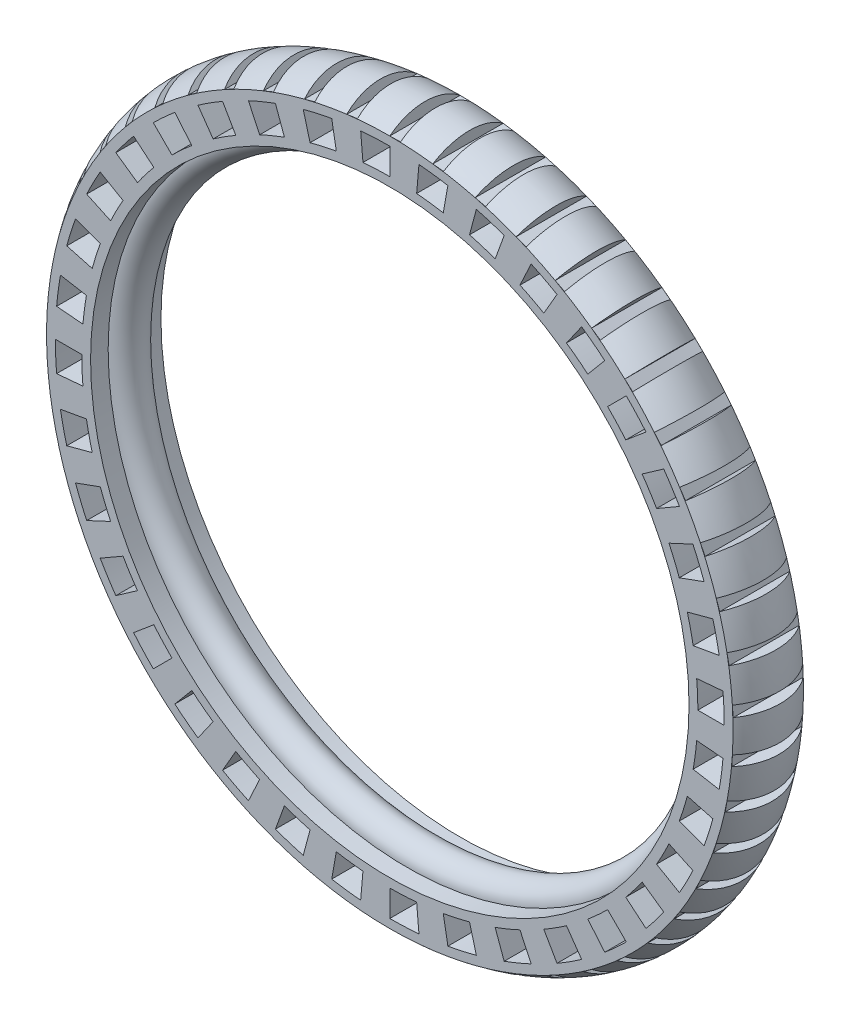
SolidWorks part; units mm, degrees
material "硅橡胶"
ref_plane "前视基准面" through (0, 0, 0) normal (0, 0, 1) x (1, 0, 0)
ref_plane "上视基准面" through (0, 0, 0) normal (0, 1, 0) x (1, 0, 0)
ref_plane "右视基准面" through (0, 0, 0) normal (1, 0, 0) x (0, 0, -1)
sketch "草图1" plane through (0, 0, 0) normal (0, 1, 0) x (1, 0, 0)
  line L0 (0, 0) -> (-43.398, 0) construction
  line L1 (0, 0) -> (0, 10.7341) construction
  line L2 (-34, 2) -> (-34, 4)
  line L3 (-34, 4) -> (-39, 4)
  line L4 (-34, -2) -> (-34, -4)
  line L5 (-34, -4) -> (-39, -4)
  arc A0 (-34, -2) -> (-34, 2) centre (-34, 0) ccw
  arc A1 (-39, 4) -> (-39, -4) centre (-34, 0) ccw
  dimension "D1" = 4
  dimension "D4" = 5
  dimension "D2" = 34
  dimension "D3" = 2
revolve "旋转1" add sketch "草图1" angle 360 about L1
sketch "草图2" plane through (0, 0, -4) normal (0, 0, -1) x (-1, 0, 0)
  line L0 (0, 0) -> (0, 48.0881) construction
  line L1 (0, 35) -> (0, 38)
  line L2 (3.0505, 34.8668) -> (3.3119, 37.8554)
  line L3 (6.0777, 34.4683) -> (6.5986, 37.4227)
  line L4 (9.0587, 33.8074) -> (9.8351, 36.7052)
  line L5 (11.9707, 32.8892) -> (12.9968, 35.7083)
  line L6 (14.7916, 31.7208) -> (16.0595, 34.4397)
  line L7 (17.5, 30.3109) -> (19, 32.909)
  line L8 (20.0752, 28.6703) -> (21.7959, 31.1278)
  line L9 (22.4976, 26.8116) -> (24.4259, 29.1097)
  line L10 (24.7487, 24.7487) -> (26.8701, 26.8701)
  line L11 (26.8116, 22.4976) -> (29.1097, 24.4259)
  line L12 (28.6703, 20.0752) -> (31.1278, 21.7959)
  line L13 (30.3109, 17.5) -> (32.909, 19)
  line L14 (31.7208, 14.7916) -> (34.4397, 16.0595)
  line L15 (32.8892, 11.9707) -> (35.7083, 12.9968)
  line L16 (33.8074, 9.0587) -> (36.7052, 9.8351)
  line L17 (34.4683, 6.0777) -> (37.4227, 6.5986)
  line L18 (34.8668, 3.0505) -> (37.8554, 3.3119)
  line L19 (35, 0) -> (38, 0)
  line L20 (34.8668, -3.0505) -> (37.8554, -3.3119)
  line L21 (34.4683, -6.0777) -> (37.4227, -6.5986)
  line L22 (33.8074, -9.0587) -> (36.7052, -9.8351)
  line L23 (32.8892, -11.9707) -> (35.7083, -12.9968)
  line L24 (31.7208, -14.7916) -> (34.4397, -16.0595)
  line L25 (30.3109, -17.5) -> (32.909, -19)
  line L26 (28.6703, -20.0752) -> (31.1278, -21.7959)
  line L27 (26.8116, -22.4976) -> (29.1097, -24.4259)
  line L28 (24.7487, -24.7487) -> (26.8701, -26.8701)
  line L29 (22.4976, -26.8116) -> (24.4259, -29.1097)
  line L30 (20.0752, -28.6703) -> (21.7959, -31.1278)
  line L31 (17.5, -30.3109) -> (19, -32.909)
  line L32 (14.7916, -31.7208) -> (16.0595, -34.4397)
  line L33 (11.9707, -32.8892) -> (12.9968, -35.7083)
  line L34 (9.0587, -33.8074) -> (9.8351, -36.7052)
  line L35 (6.0777, -34.4683) -> (6.5986, -37.4227)
  line L36 (3.0505, -34.8668) -> (3.3119, -37.8554)
  line L37 (0, -35) -> (0, -38)
  line L38 (-3.0505, -34.8668) -> (-3.3119, -37.8554)
  line L39 (-6.0777, -34.4683) -> (-6.5986, -37.4227)
  line L40 (-9.0587, -33.8074) -> (-9.8351, -36.7052)
  line L41 (-11.9707, -32.8892) -> (-12.9968, -35.7083)
  line L42 (-14.7916, -31.7208) -> (-16.0595, -34.4397)
  line L43 (-17.5, -30.3109) -> (-19, -32.909)
  line L44 (-20.0752, -28.6703) -> (-21.7959, -31.1278)
  line L45 (-22.4976, -26.8116) -> (-24.4259, -29.1097)
  line L46 (-24.7487, -24.7487) -> (-26.8701, -26.8701)
  line L47 (-26.8116, -22.4976) -> (-29.1097, -24.4259)
  line L48 (-28.6703, -20.0752) -> (-31.1278, -21.7959)
  line L49 (-30.3109, -17.5) -> (-32.909, -19)
  line L50 (-31.7208, -14.7916) -> (-34.4397, -16.0595)
  line L51 (-32.8892, -11.9707) -> (-35.7083, -12.9968)
  line L52 (-33.8074, -9.0587) -> (-36.7052, -9.8351)
  line L53 (-34.4683, -6.0777) -> (-37.4227, -6.5986)
  line L54 (-34.8668, -3.0505) -> (-37.8554, -3.3119)
  line L55 (-35, 0) -> (-38, 0)
  line L56 (-34.8668, 3.0505) -> (-37.8554, 3.3119)
  line L57 (-34.4683, 6.0777) -> (-37.4227, 6.5986)
  line L58 (-33.8074, 9.0587) -> (-36.7052, 9.8351)
  line L59 (-32.8892, 11.9707) -> (-35.7083, 12.9968)
  line L60 (-31.7208, 14.7916) -> (-34.4397, 16.0595)
  line L61 (-30.3109, 17.5) -> (-32.909, 19)
  line L62 (-28.6703, 20.0752) -> (-31.1278, 21.7959)
  line L63 (-26.8116, 22.4976) -> (-29.1097, 24.4259)
  line L64 (-24.7487, 24.7487) -> (-26.8701, 26.8701)
  line L65 (-22.4976, 26.8116) -> (-24.4259, 29.1097)
  line L66 (-20.0752, 28.6703) -> (-21.7959, 31.1278)
  line L67 (-17.5, 30.3109) -> (-19, 32.909)
  line L68 (-14.7916, 31.7208) -> (-16.0595, 34.4397)
  line L69 (-11.9707, 32.8892) -> (-12.9968, 35.7083)
  line L70 (-9.0587, 33.8074) -> (-9.8351, 36.7052)
  line L71 (-6.0777, 34.4683) -> (-6.5986, 37.4227)
  line L72 (-3.0505, 34.8668) -> (-3.3119, 37.8554)
  line L73 (3.9481, 40.8271) -> (5.1387, 40.6767)
  line L74 (-1.2, 41) -> (0, 41)
  line L75 (-1.2, 41) -> (-1.2, 39)
  line L76 (-1.2, 39) -> (0, 39)
  line L77 (0, 41) -> (0, 39)
  line L78 (3.9481, 40.8271) -> (3.6975, 38.8429)
  line L79 (5.1387, 40.6767) -> (4.888, 38.6925)
  line L80 (3.6975, 38.8429) -> (4.888, 38.6925)
  line L81 (9.034, 40.0103) -> (10.1963, 39.7119)
  line L82 (9.034, 40.0103) -> (8.5366, 38.0732)
  line L83 (10.1963, 39.7119) -> (9.6989, 37.7747)
  line L84 (8.5366, 38.0732) -> (9.6989, 37.7747)
  line L85 (13.9774, 38.5626) -> (15.0931, 38.1208)
  line L86 (13.9774, 38.5626) -> (13.2411, 36.703)
  line L87 (15.0931, 38.1208) -> (14.3569, 36.2613)
  line L88 (13.2411, 36.703) -> (14.3569, 36.2613)
  line L89 (18.7003, 36.5067) -> (19.7519, 35.9286)
  line L90 (18.7003, 36.5067) -> (17.7368, 34.7541)
  line L91 (19.7519, 35.9286) -> (18.7884, 34.176)
  line L92 (17.7368, 34.7541) -> (18.7884, 34.176)
  line L93 (23.1284, 33.875) -> (24.0992, 33.1697)
  line L94 (23.1284, 33.875) -> (21.9528, 32.257)
  line L95 (24.0992, 33.1697) -> (22.9236, 31.5517)
  line L96 (21.9528, 32.257) -> (22.9236, 31.5517)
  line L97 (27.1917, 30.7092) -> (28.0664, 29.8877)
  line L98 (27.1917, 30.7092) -> (25.8226, 29.2512)
  line L99 (28.0664, 29.8877) -> (26.6973, 28.4298)
  line L100 (25.8226, 29.2512) -> (26.6973, 28.4298)
  line L101 (30.8261, 27.059) -> (31.591, 26.1344)
  line L102 (30.8261, 27.059) -> (29.2851, 25.7842)
  line L103 (31.591, 26.1344) -> (30.05, 24.8595)
  line L104 (29.2851, 25.7842) -> (30.05, 24.8595)
  line L105 (33.9745, 22.9821) -> (34.6174, 21.9689)
  line L106 (33.9745, 22.9821) -> (32.2858, 21.9104)
  line L107 (34.6174, 21.9689) -> (32.9288, 20.8972)
  line L108 (32.2858, 21.9104) -> (32.9288, 20.8972)
  line L109 (36.587, 18.5427) -> (37.0979, 17.457)
  line L110 (36.587, 18.5427) -> (34.7773, 17.6912)
  line L111 (37.0979, 17.457) -> (35.2883, 16.6054)
  line L112 (34.7773, 17.6912) -> (35.2883, 16.6054)
  line L113 (38.6225, 13.811) -> (38.9933, 12.6697)
  line L114 (38.6225, 13.811) -> (36.7204, 13.1929)
  line L115 (38.9933, 12.6697) -> (37.0912, 12.0517)
  line L116 (36.7204, 13.1929) -> (37.0912, 12.0517)
  line L117 (40.0489, 8.8614) -> (40.2738, 7.6826)
  line L118 (40.0489, 8.8614) -> (38.0843, 8.4866)
  line L119 (40.2738, 7.6826) -> (38.3092, 7.3079)
  line L120 (38.0843, 8.4866) -> (38.3092, 7.3079)
  line L121 (40.8437, 3.772) -> (40.9191, 2.5744)
  line L122 (40.8437, 3.772) -> (38.8477, 3.6465)
  line L123 (40.9191, 2.5744) -> (38.923, 2.4488)
  line L124 (38.8477, 3.6465) -> (38.923, 2.4488)
  line L125 (40.9944, -1.3768) -> (40.9191, -2.5744)
  line L126 (40.9944, -1.3768) -> (38.9984, -1.2512)
  line L127 (40.9191, -2.5744) -> (38.923, -2.4488)
  line L128 (38.9984, -1.2512) -> (38.923, -2.4488)
  line L129 (40.4986, -6.5039) -> (40.2738, -7.6826)
  line L130 (40.4986, -6.5039) -> (38.5341, -6.1291)
  line L131 (40.2738, -7.6826) -> (38.3092, -7.3079)
  line L132 (38.5341, -6.1291) -> (38.3092, -7.3079)
  line L133 (39.3641, -11.5284) -> (38.9933, -12.6697)
  line L134 (39.3641, -11.5284) -> (37.462, -10.9104)
  line L135 (38.9933, -12.6697) -> (37.0912, -12.0517)
  line L136 (37.462, -10.9104) -> (37.0912, -12.0517)
  line L137 (37.6088, -16.3712) -> (37.0979, -17.457)
  line L138 (37.6088, -16.3712) -> (35.7992, -15.5196)
  line L139 (37.0979, -17.457) -> (35.2883, -16.6054)
  line L140 (35.7992, -15.5196) -> (35.2883, -16.6054)
  line L141 (35.2604, -20.9557) -> (34.6174, -21.9689)
  line L142 (35.2604, -20.9557) -> (33.5718, -19.8841)
  line L143 (34.6174, -21.9689) -> (32.9288, -20.8972)
  line L144 (33.5718, -19.8841) -> (32.9288, -20.8972)
  line L145 (32.356, -25.2098) -> (31.591, -26.1344)
  line L146 (32.356, -25.2098) -> (30.8149, -23.9349)
  line L147 (31.591, -26.1344) -> (30.05, -24.8595)
  line L148 (30.8149, -23.9349) -> (30.05, -24.8595)
  line L149 (28.9412, -29.0663) -> (28.0664, -29.8877)
  line L150 (28.9412, -29.0663) -> (27.5721, -27.6083)
  line L151 (28.0664, -29.8877) -> (26.6973, -28.4298)
  line L152 (27.5721, -27.6083) -> (26.6973, -28.4298)
  line L153 (25.07, -32.4644) -> (24.0992, -33.1697)
  line L154 (25.07, -32.4644) -> (23.8944, -30.8463)
  line L155 (24.0992, -33.1697) -> (22.9236, -31.5517)
  line L156 (23.8944, -30.8463) -> (22.9236, -31.5517)
  line L157 (20.8035, -35.3505) -> (19.7519, -35.9286)
  line L158 (20.8035, -35.3505) -> (19.84, -33.5979)
  line L159 (19.7519, -35.9286) -> (18.7884, -34.176)
  line L160 (19.84, -33.5979) -> (18.7884, -34.176)
  line L161 (16.2088, -37.6791) -> (15.0931, -38.1208)
  line L162 (16.2088, -37.6791) -> (15.4726, -35.8195)
  line L163 (15.0931, -38.1208) -> (14.3569, -36.2613)
  line L164 (15.4726, -35.8195) -> (14.3569, -36.2613)
  line L165 (11.3586, -39.4135) -> (10.1963, -39.7119)
  line L166 (11.3586, -39.4135) -> (10.8612, -37.4763)
  line L167 (10.1963, -39.7119) -> (9.6989, -37.7747)
  line L168 (10.8612, -37.4763) -> (9.6989, -37.7747)
  line L169 (6.3292, -40.5263) -> (5.1387, -40.6767)
  line L170 (6.3292, -40.5263) -> (6.0785, -38.5421)
  line L171 (5.1387, -40.6767) -> (4.888, -38.6925)
  line L172 (6.0785, -38.5421) -> (4.888, -38.6925)
  line L173 (1.2, -41) -> (0, -41)
  line L174 (1.2, -41) -> (1.2, -39)
  line L175 (0, -41) -> (0, -39)
  line L176 (1.2, -39) -> (0, -39)
  line L177 (-3.9481, -40.8271) -> (-5.1387, -40.6767)
  line L178 (-3.9481, -40.8271) -> (-3.6975, -38.8429)
  line L179 (-5.1387, -40.6767) -> (-4.888, -38.6925)
  line L180 (-3.6975, -38.8429) -> (-4.888, -38.6925)
  line L181 (-9.034, -40.0103) -> (-10.1963, -39.7119)
  line L182 (-9.034, -40.0103) -> (-8.5366, -38.0732)
  line L183 (-10.1963, -39.7119) -> (-9.6989, -37.7747)
  line L184 (-8.5366, -38.0732) -> (-9.6989, -37.7747)
  line L185 (-13.9774, -38.5626) -> (-15.0931, -38.1208)
  line L186 (-13.9774, -38.5626) -> (-13.2411, -36.703)
  line L187 (-15.0931, -38.1208) -> (-14.3569, -36.2613)
  line L188 (-13.2411, -36.703) -> (-14.3569, -36.2613)
  line L189 (-18.7003, -36.5067) -> (-19.7519, -35.9286)
  line L190 (-18.7003, -36.5067) -> (-17.7368, -34.7541)
  line L191 (-19.7519, -35.9286) -> (-18.7884, -34.176)
  line L192 (-17.7368, -34.7541) -> (-18.7884, -34.176)
  line L193 (-23.1284, -33.875) -> (-24.0992, -33.1697)
  line L194 (-23.1284, -33.875) -> (-21.9528, -32.257)
  line L195 (-24.0992, -33.1697) -> (-22.9236, -31.5517)
  line L196 (-21.9528, -32.257) -> (-22.9236, -31.5517)
  line L197 (-27.1917, -30.7092) -> (-28.0664, -29.8877)
  line L198 (-27.1917, -30.7092) -> (-25.8226, -29.2512)
  line L199 (-28.0664, -29.8877) -> (-26.6973, -28.4298)
  line L200 (-25.8226, -29.2512) -> (-26.6973, -28.4298)
  line L201 (-30.8261, -27.059) -> (-31.591, -26.1344)
  line L202 (-30.8261, -27.059) -> (-29.2851, -25.7842)
  line L203 (-31.591, -26.1344) -> (-30.05, -24.8595)
  line L204 (-29.2851, -25.7842) -> (-30.05, -24.8595)
  line L205 (-33.9745, -22.9821) -> (-34.6174, -21.9689)
  line L206 (-33.9745, -22.9821) -> (-32.2858, -21.9104)
  line L207 (-34.6174, -21.9689) -> (-32.9288, -20.8972)
  line L208 (-32.2858, -21.9104) -> (-32.9288, -20.8972)
  line L209 (-36.587, -18.5427) -> (-37.0979, -17.457)
  line L210 (-36.587, -18.5427) -> (-34.7773, -17.6912)
  line L211 (-37.0979, -17.457) -> (-35.2883, -16.6054)
  line L212 (-34.7773, -17.6912) -> (-35.2883, -16.6054)
  line L213 (-38.6225, -13.811) -> (-38.9933, -12.6697)
  line L214 (-38.6225, -13.811) -> (-36.7204, -13.1929)
  line L215 (-38.9933, -12.6697) -> (-37.0912, -12.0517)
  line L216 (-36.7204, -13.1929) -> (-37.0912, -12.0517)
  line L217 (-40.0489, -8.8614) -> (-40.2738, -7.6826)
  line L218 (-40.0489, -8.8614) -> (-38.0843, -8.4866)
  line L219 (-40.2738, -7.6826) -> (-38.3092, -7.3079)
  line L220 (-38.0843, -8.4866) -> (-38.3092, -7.3079)
  line L221 (-40.8437, -3.772) -> (-40.9191, -2.5744)
  line L222 (-40.8437, -3.772) -> (-38.8477, -3.6465)
  line L223 (-40.9191, -2.5744) -> (-38.923, -2.4488)
  line L224 (-38.8477, -3.6465) -> (-38.923, -2.4488)
  line L225 (-40.9944, 1.3768) -> (-40.9191, 2.5744)
  line L226 (-40.9944, 1.3768) -> (-38.9984, 1.2512)
  line L227 (-40.9191, 2.5744) -> (-38.923, 2.4488)
  line L228 (-38.9984, 1.2512) -> (-38.923, 2.4488)
  line L229 (-40.4986, 6.5039) -> (-40.2738, 7.6826)
  line L230 (-40.4986, 6.5039) -> (-38.5341, 6.1291)
  line L231 (-40.2738, 7.6826) -> (-38.3092, 7.3079)
  line L232 (-38.5341, 6.1291) -> (-38.3092, 7.3079)
  line L233 (-39.3641, 11.5284) -> (-38.9933, 12.6697)
  line L234 (-39.3641, 11.5284) -> (-37.462, 10.9104)
  line L235 (-38.9933, 12.6697) -> (-37.0912, 12.0517)
  line L236 (-37.462, 10.9104) -> (-37.0912, 12.0517)
  line L237 (-37.6088, 16.3712) -> (-37.0979, 17.457)
  line L238 (-37.6088, 16.3712) -> (-35.7992, 15.5196)
  line L239 (-37.0979, 17.457) -> (-35.2883, 16.6054)
  line L240 (-35.7992, 15.5196) -> (-35.2883, 16.6054)
  line L241 (-35.2604, 20.9557) -> (-34.6174, 21.9689)
  line L242 (-35.2604, 20.9557) -> (-33.5718, 19.8841)
  line L243 (-34.6174, 21.9689) -> (-32.9288, 20.8972)
  line L244 (-33.5718, 19.8841) -> (-32.9288, 20.8972)
  line L245 (-32.356, 25.2098) -> (-31.591, 26.1344)
  line L246 (-32.356, 25.2098) -> (-30.8149, 23.9349)
  line L247 (-31.591, 26.1344) -> (-30.05, 24.8595)
  line L248 (-30.8149, 23.9349) -> (-30.05, 24.8595)
  line L249 (-28.9412, 29.0663) -> (-28.0664, 29.8877)
  line L250 (-28.9412, 29.0663) -> (-27.5721, 27.6083)
  line L251 (-28.0664, 29.8877) -> (-26.6973, 28.4298)
  line L252 (-27.5721, 27.6083) -> (-26.6973, 28.4298)
  line L253 (-25.07, 32.4644) -> (-24.0992, 33.1697)
  line L254 (-25.07, 32.4644) -> (-23.8944, 30.8463)
  line L255 (-24.0992, 33.1697) -> (-22.9236, 31.5517)
  line L256 (-23.8944, 30.8463) -> (-22.9236, 31.5517)
  line L257 (-20.8035, 35.3505) -> (-19.7519, 35.9286)
  line L258 (-20.8035, 35.3505) -> (-19.84, 33.5979)
  line L259 (-19.7519, 35.9286) -> (-18.7884, 34.176)
  line L260 (-19.84, 33.5979) -> (-18.7884, 34.176)
  line L261 (-16.2088, 37.6791) -> (-15.0931, 38.1208)
  line L262 (-16.2088, 37.6791) -> (-15.4726, 35.8195)
  line L263 (-15.0931, 38.1208) -> (-14.3569, 36.2613)
  line L264 (-15.4726, 35.8195) -> (-14.3569, 36.2613)
  line L265 (-11.3586, 39.4135) -> (-10.1963, 39.7119)
  line L266 (-11.3586, 39.4135) -> (-10.8612, 37.4763)
  line L267 (-10.1963, 39.7119) -> (-9.6989, 37.7747)
  line L268 (-10.8612, 37.4763) -> (-9.6989, 37.7747)
  line L269 (-6.3292, 40.5263) -> (-5.1387, 40.6767)
  line L270 (-6.3292, 40.5263) -> (-6.0785, 38.5421)
  line L271 (-5.1387, 40.6767) -> (-4.888, 38.6925)
  line L272 (-6.0785, 38.5421) -> (-4.888, 38.6925)
  arc A0 (3.0505, 34.8668) -> (0, 35) centre (0, 0) ccw
  arc A1 (3.3119, 37.8554) -> (0, 38) centre (0, 0) ccw
  arc A2 (9.0587, 33.8074) -> (6.0777, 34.4683) centre (0, 0) ccw
  arc A3 (9.8351, 36.7052) -> (6.5986, 37.4227) centre (0, 0) ccw
  arc A4 (14.7916, 31.7208) -> (11.9707, 32.8892) centre (0, 0) ccw
  arc A5 (16.0595, 34.4397) -> (12.9968, 35.7083) centre (0, 0) ccw
  arc A6 (20.0752, 28.6703) -> (17.5, 30.3109) centre (0, 0) ccw
  arc A7 (21.7959, 31.1278) -> (19, 32.909) centre (0, 0) ccw
  arc A8 (24.7487, 24.7487) -> (22.4976, 26.8116) centre (0, 0) ccw
  arc A9 (26.8701, 26.8701) -> (24.4259, 29.1097) centre (0, 0) ccw
  arc A10 (28.6703, 20.0752) -> (26.8116, 22.4976) centre (0, 0) ccw
  arc A11 (31.1278, 21.7959) -> (29.1097, 24.4259) centre (0, 0) ccw
  arc A12 (31.7208, 14.7916) -> (30.3109, 17.5) centre (0, 0) ccw
  arc A13 (34.4397, 16.0595) -> (32.909, 19) centre (0, 0) ccw
  arc A14 (33.8074, 9.0587) -> (32.8892, 11.9707) centre (0, 0) ccw
  arc A15 (36.7052, 9.8351) -> (35.7083, 12.9968) centre (0, 0) ccw
  arc A16 (34.8668, 3.0505) -> (34.4683, 6.0777) centre (0, 0) ccw
  arc A17 (37.8554, 3.3119) -> (37.4227, 6.5986) centre (0, 0) ccw
  arc A18 (34.8668, -3.0505) -> (35, 0) centre (0, 0) ccw
  arc A19 (37.8554, -3.3119) -> (38, 0) centre (0, 0) ccw
  arc A20 (33.8074, -9.0587) -> (34.4683, -6.0777) centre (0, 0) ccw
  arc A21 (36.7052, -9.8351) -> (37.4227, -6.5986) centre (0, 0) ccw
  arc A22 (31.7208, -14.7916) -> (32.8892, -11.9707) centre (0, 0) ccw
  arc A23 (34.4397, -16.0595) -> (35.7083, -12.9968) centre (0, 0) ccw
  arc A24 (28.6703, -20.0752) -> (30.3109, -17.5) centre (0, 0) ccw
  arc A25 (31.1278, -21.7959) -> (32.909, -19) centre (0, 0) ccw
  arc A26 (24.7487, -24.7487) -> (26.8116, -22.4976) centre (0, 0) ccw
  arc A27 (26.8701, -26.8701) -> (29.1097, -24.4259) centre (0, 0) ccw
  arc A28 (20.0752, -28.6703) -> (22.4976, -26.8116) centre (0, 0) ccw
  arc A29 (21.7959, -31.1278) -> (24.4259, -29.1097) centre (0, 0) ccw
  arc A30 (14.7916, -31.7208) -> (17.5, -30.3109) centre (0, 0) ccw
  arc A31 (16.0595, -34.4397) -> (19, -32.909) centre (0, 0) ccw
  arc A32 (9.0587, -33.8074) -> (11.9707, -32.8892) centre (0, 0) ccw
  arc A33 (9.8351, -36.7052) -> (12.9968, -35.7083) centre (0, 0) ccw
  arc A34 (3.0505, -34.8668) -> (6.0777, -34.4683) centre (0, 0) ccw
  arc A35 (3.3119, -37.8554) -> (6.5986, -37.4227) centre (0, 0) ccw
  arc A36 (-3.0505, -34.8668) -> (0, -35) centre (0, 0) ccw
  arc A37 (-3.3119, -37.8554) -> (0, -38) centre (0, 0) ccw
  arc A38 (-9.0587, -33.8074) -> (-6.0777, -34.4683) centre (0, 0) ccw
  arc A39 (-9.8351, -36.7052) -> (-6.5986, -37.4227) centre (0, 0) ccw
  arc A40 (-14.7916, -31.7208) -> (-11.9707, -32.8892) centre (0, 0) ccw
  arc A41 (-16.0595, -34.4397) -> (-12.9968, -35.7083) centre (0, 0) ccw
  arc A42 (-20.0752, -28.6703) -> (-17.5, -30.3109) centre (0, 0) ccw
  arc A43 (-21.7959, -31.1278) -> (-19, -32.909) centre (0, 0) ccw
  arc A44 (-24.7487, -24.7487) -> (-22.4976, -26.8116) centre (0, 0) ccw
  arc A45 (-26.8701, -26.8701) -> (-24.4259, -29.1097) centre (0, 0) ccw
  arc A46 (-28.6703, -20.0752) -> (-26.8116, -22.4976) centre (0, 0) ccw
  arc A47 (-31.1278, -21.7959) -> (-29.1097, -24.4259) centre (0, 0) ccw
  arc A48 (-31.7208, -14.7916) -> (-30.3109, -17.5) centre (0, 0) ccw
  arc A49 (-34.4397, -16.0595) -> (-32.909, -19) centre (0, 0) ccw
  arc A50 (-33.8074, -9.0587) -> (-32.8892, -11.9707) centre (0, 0) ccw
  arc A51 (-36.7052, -9.8351) -> (-35.7083, -12.9968) centre (0, 0) ccw
  arc A52 (-34.8668, -3.0505) -> (-34.4683, -6.0777) centre (0, 0) ccw
  arc A53 (-37.8554, -3.3119) -> (-37.4227, -6.5986) centre (0, 0) ccw
  arc A54 (-34.8668, 3.0505) -> (-35, 0) centre (0, 0) ccw
  arc A55 (-37.8554, 3.3119) -> (-38, 0) centre (0, 0) ccw
  arc A56 (-33.8074, 9.0587) -> (-34.4683, 6.0777) centre (0, 0) ccw
  arc A57 (-36.7052, 9.8351) -> (-37.4227, 6.5986) centre (0, 0) ccw
  arc A58 (-31.7208, 14.7916) -> (-32.8892, 11.9707) centre (0, 0) ccw
  arc A59 (-34.4397, 16.0595) -> (-35.7083, 12.9968) centre (0, 0) ccw
  arc A60 (-28.6703, 20.0752) -> (-30.3109, 17.5) centre (0, 0) ccw
  arc A61 (-31.1278, 21.7959) -> (-32.909, 19) centre (0, 0) ccw
  arc A62 (-24.7487, 24.7487) -> (-26.8116, 22.4976) centre (0, 0) ccw
  arc A63 (-26.8701, 26.8701) -> (-29.1097, 24.4259) centre (0, 0) ccw
  arc A64 (-20.0752, 28.6703) -> (-22.4976, 26.8116) centre (0, 0) ccw
  arc A65 (-21.7959, 31.1278) -> (-24.4259, 29.1097) centre (0, 0) ccw
  arc A66 (-14.7916, 31.7208) -> (-17.5, 30.3109) centre (0, 0) ccw
  arc A67 (-16.0595, 34.4397) -> (-19, 32.909) centre (0, 0) ccw
  arc A68 (-9.0587, 33.8074) -> (-11.9707, 32.8892) centre (0, 0) ccw
  arc A69 (-9.8351, 36.7052) -> (-12.9968, 35.7083) centre (0, 0) ccw
  arc A70 (-3.0505, 34.8668) -> (-6.0777, 34.4683) centre (0, 0) ccw
  arc A71 (-3.3119, 37.8554) -> (-6.5986, 37.4227) centre (0, 0) ccw
  dimension "D1" = 5
  dimension "D2" = 38
  dimension "D3" = 35
  dimension "D5" = 1.2
  dimension "D6" = 39
  dimension "D7" = 2
  dimension "D4" = 36
  dimension "D8" = 50
extrude "切除-拉伸1" cut sketch "草图2" against normal up to next (8 mm away)
